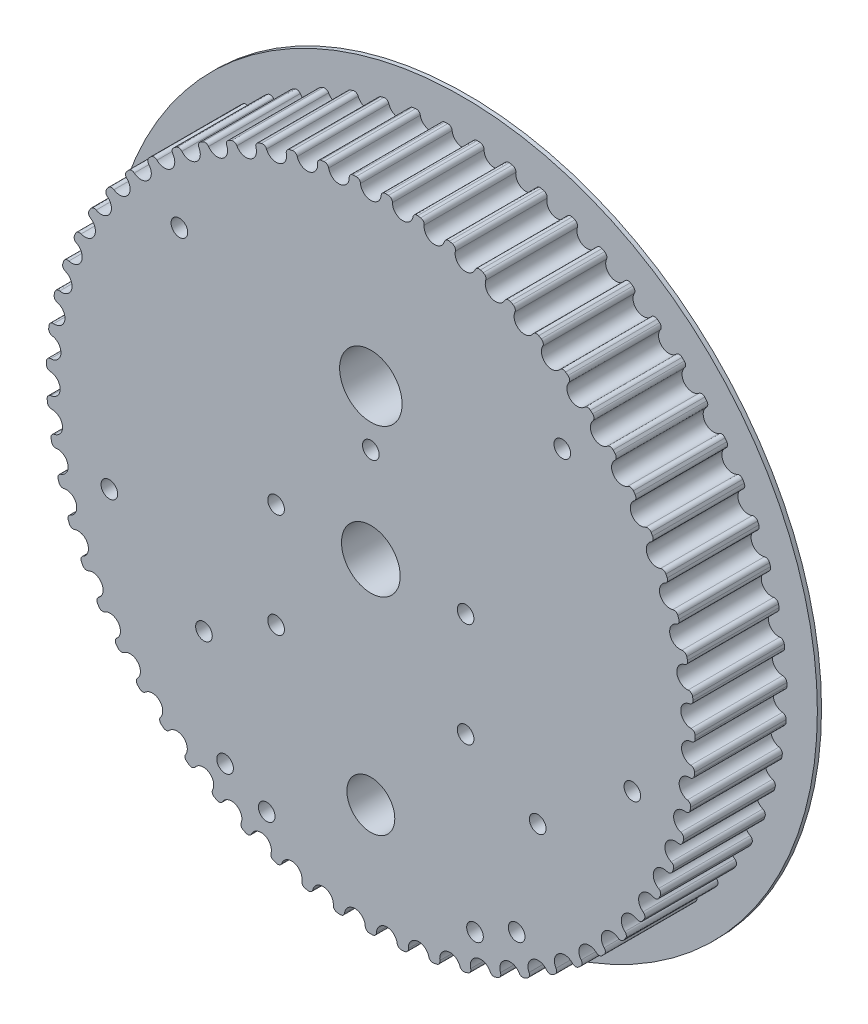
SolidWorks part; units mm, degrees
material "PETG"
ref_plane "Front Plane" through (0, 0, 0) normal (0, 0, 1) x (1, 0, 0)
ref_plane "Top Plane" through (0, 0, 0) normal (0, 1, 0) x (1, 0, 0)
ref_plane "Right Plane" through (0, 0, 0) normal (1, 0, 0) x (0, 0, -1)
sketch "Sketch1" plane through (0, 0, 0) normal (0, 0, 1) x (1, 0, 0)
  line L0 (0, 0) -> (0, 50000) construction
  line L1 (0, 0) -> (3.9983, 80.1144) construction
  line L2 (0, 0) -> (-3.9983, 80.1144) construction
  circle A0 centre (0, 0) radius 80.2141 construction
  arc A1 (-2.4815, 76.9081) -> (2.4815, 76.9081) centre (0, 77.1141) ccw
  arc A2 (3.8832, 77.8073) -> (-3.8832, 77.8073) centre (0, 0) ccw construction
  arc A3 (-2.4815, 76.9081) -> (-3.5233, 77.8244) centre (-3.478, 76.8254) ccw
  arc A4 (3.5233, 77.8244) -> (2.4815, 76.9081) centre (3.478, 76.8254) ccw
  arc A5 (-3.5233, 77.8244) -> (-3.8832, 77.8073) centre (0, 0) ccw
  arc A6 (3.5233, 77.8244) -> (3.8832, 77.8073) centre (0, 0) cw
  arc A7 (4.243, 77.7885) -> (3.8832, 77.8073) centre (0, 0) ccw
  arc A8 (5.1884, 76.773) -> (4.243, 77.7885) centre (4.1886, 76.7899) ccw
  arc A9 (5.1884, 76.773) -> (10.1267, 76.2789) centre (7.6781, 76.7309) ccw
  arc A10 (11.2546, 77.0868) -> (10.1267, 76.2789) centre (11.1101, 76.0973) ccw
  arc A11 (11.2546, 77.0868) -> (11.611, 77.034) centre (0, 0) cw
  arc A12 (11.9672, 76.9794) -> (11.611, 77.034) centre (0, 0) ccw
  arc A13 (12.8068, 75.8749) -> (11.9672, 76.9794) centre (11.8136, 75.9913) ccw
  arc A14 (12.8068, 75.8749) -> (17.6713, 74.8915) centre (15.2799, 75.5851) ccw
  arc A15 (18.874, 75.5832) -> (17.6713, 74.8915) centre (18.6317, 74.613) ccw
  arc A16 (18.874, 75.5832) -> (19.2234, 75.4951) centre (0, 0) cw
  arc A17 (19.5724, 75.4054) -> (19.2234, 75.4951) centre (0, 0) ccw
  arc A18 (20.2978, 74.2227) -> (19.5724, 75.4054) centre (19.3212, 74.4374) ccw
  arc A19 (20.2978, 74.2227) -> (25.0403, 72.7599) centre (22.7298, 73.6881) ccw
  arc A20 (26.3059, 73.3284) -> (25.0403, 72.7599) centre (25.9682, 72.3871) ccw
  arc A21 (26.3059, 73.3284) -> (26.6448, 73.2059) centre (0, 0) cw
  arc A22 (26.9831, 73.0819) -> (26.6448, 73.2059) centre (0, 0) ccw
  arc A23 (27.5872, 71.8329) -> (26.9831, 73.0819) centre (26.6367, 72.1438) ccw
  arc A24 (27.5872, 71.8329) -> (32.1604, 69.9051) centre (29.9538, 71.0588) ccw
  arc A25 (33.4763, 70.3448) -> (32.1604, 69.9051) centre (33.0466, 69.4418) ccw
  arc A26 (33.4763, 70.3448) -> (33.8013, 70.1892) centre (0, 0) cw
  arc A27 (34.1256, 70.0321) -> (33.8013, 70.1892) centre (0, 0) ccw
  arc A28 (34.6023, 68.7291) -> (34.1256, 70.0321) centre (33.6876, 69.1331) ccw
  arc A29 (34.6023, 68.7291) -> (38.9609, 66.3556) centre (36.8801, 67.7233) ccw
  arc A30 (40.314, 66.662) -> (38.9609, 66.3556) centre (39.7965, 65.8063) ccw
  arc A31 (40.314, 66.662) -> (40.6219, 66.4749) centre (0, 0) cw
  arc A32 (40.929, 66.2862) -> (40.6219, 66.4749) centre (0, 0) ccw
  arc A33 (41.2736, 64.9423) -> (40.929, 66.2862) centre (40.4036, 65.4354) ccw
  arc A34 (41.2736, 64.9423) -> (45.3742, 62.1466) centre (43.4399, 63.7147) ccw
  arc A35 (46.7511, 62.3168) -> (45.3742, 62.1466) centre (46.151, 61.5169) ccw
  arc A36 (46.7511, 62.3168) -> (47.0388, 62.0999) centre (0, 0) cw
  arc A37 (47.3256, 61.8816) -> (47.0388, 62.0999) centre (0, 0) ccw
  arc A38 (47.5347, 60.5101) -> (47.3256, 61.8816) centre (46.7181, 61.0873) ccw
  arc A39 (47.5347, 60.5101) -> (51.3365, 57.32) centre (49.568, 59.0728) ccw
  arc A40 (52.7235, 57.3522) -> (51.3365, 57.32) centre (52.0467, 56.616) ccw
  arc A41 (52.7235, 57.3522) -> (52.9882, 57.1077) centre (0, 0) cw
  arc A42 (53.2518, 56.862) -> (52.9882, 57.1077) centre (0, 0) ccw
  arc A43 (53.3233, 55.4765) -> (53.2518, 56.862) centre (52.5683, 56.1321) ccw
  arc A44 (53.3233, 55.4765) -> (56.7886, 51.9237) centre (55.2034, 53.8439) ccw
  arc A45 (58.172, 51.8177) -> (56.7886, 51.9237) centre (57.4253, 51.1525) ccw
  arc A46 (58.172, 51.8177) -> (58.411, 51.548) centre (0, 0) cw
  arc A47 (58.6488, 51.2773) -> (58.411, 51.548) centre (0, 0) ccw
  arc A48 (58.582, 49.8915) -> (58.6488, 51.2773) centre (57.896, 50.6191) ccw
  arc A49 (58.582, 49.8915) -> (61.6764, 46.0113) centre (60.2902, 48.0798) ccw
  arc A50 (63.0423, 45.7681) -> (61.6764, 46.0113) centre (62.233, 45.1806) ccw
  arc A51 (63.0423, 45.7681) -> (63.2533, 45.476) centre (0, 0) cw
  arc A52 (63.463, 45.183) -> (63.2533, 45.476) centre (0, 0) ccw
  arc A53 (63.2585, 43.8107) -> (63.463, 45.183) centre (62.6483, 44.603) ccw
  arc A54 (63.2585, 43.8107) -> (65.9511, 39.6417) centre (64.7778, 41.838) ccw
  arc A55 (67.286, 39.2637) -> (65.9511, 39.6417) centre (66.4223, 38.7597) ccw
  arc A56 (67.286, 39.2637) -> (67.4669, 38.952) centre (0, 0) cw
  arc A57 (67.6464, 38.6396) -> (67.4669, 38.952) centre (0, 0) ccw
  arc A58 (67.3063, 37.2945) -> (67.6464, 38.6396) centre (66.778, 38.1436) ccw
  arc A59 (67.3063, 37.2945) -> (69.5704, 32.8781) centre (68.6217, 35.1803) ccw
  arc A60 (70.8611, 32.3691) -> (69.5704, 32.8781) centre (69.9515, 31.9536) ccw
  arc A61 (70.8611, 32.3691) -> (71.01, 32.0409) centre (0, 0) cw
  arc A62 (71.1575, 31.7122) -> (71.01, 32.0409) centre (0, 0) ccw
  arc A63 (70.6852, 30.4076) -> (71.1575, 31.7122) centre (70.2441, 31.3051) ccw
  arc A64 (70.6852, 30.4076) -> (72.4983, 25.7878) centre (71.7835, 28.1729) ccw
  arc A65 (73.7319, 25.1527) -> (72.4983, 25.7878) centre (72.7854, 24.8299) ccw
  arc A66 (73.7319, 25.1527) -> (73.8474, 24.8114) centre (0, 0) cw
  arc A67 (73.9614, 24.4696) -> (73.8474, 24.8114) centre (0, 0) ccw
  arc A68 (73.3615, 23.2186) -> (73.9614, 24.4696) centre (73.012, 24.1555) ccw
  arc A69 (73.3615, 23.2186) -> (74.7057, 18.4411) centre (74.2319, 20.8856) ccw
  arc A70 (75.8699, 17.6864) -> (74.7057, 18.4411) centre (74.896, 17.4594) ccw
  arc A71 (75.8699, 17.6864) -> (75.9509, 17.3353) centre (0, 0) cw
  arc A72 (76.0302, 16.9838) -> (75.9509, 17.3353) centre (0, 0) ccw
  arc A73 (75.3088, 15.7987) -> (76.0302, 16.9838) centre (75.0543, 16.7658) ccw
  arc A74 (75.3088, 15.7987) -> (76.1706, 10.9112) centre (75.9426, 13.3907) ccw
  arc A75 (77.2539, 10.0443) -> (76.1706, 10.9112) centre (76.2622, 9.9154) ccw
  arc A76 (77.2539, 10.0443) -> (77.2995, 9.6869) centre (0, 0) cw
  arc A77 (77.3435, 9.3292) -> (77.2995, 9.6869) centre (0, 0) ccw
  arc A78 (76.5076, 8.2219) -> (77.3435, 9.3292) centre (76.3507, 9.2095) ccw
  arc A79 (76.5076, 8.2219) -> (76.8785, 3.2728) centre (76.8985, 5.7627) ccw
  arc A80 (77.8701, 2.3024) -> (76.8785, 3.2728) centre (76.8705, 2.2729) ccw
  arc A81 (77.8701, 2.3024) -> (77.8799, 1.9422) centre (0, 0) cw
  arc A82 (77.888, 1.582) -> (77.8799, 1.9422) centre (0, 0) ccw
  arc A83 (76.9461, 0.5633) -> (77.888, 1.582) centre (76.8882, 1.5616) ccw
  arc A84 (76.9461, 0.5633) -> (76.8224, -4.3981) centre (77.0901, -1.9225) ccw
  arc A85 (77.7124, -5.4624) -> (76.8224, -4.3981) centre (76.7148, -5.3923) ccw
  arc A86 (77.7124, -5.4624) -> (77.6863, -5.8218) centre (0, 0) cw
  arc A87 (77.6585, -6.181) -> (77.6863, -5.8218) centre (0, 0) ccw
  arc A88 (76.6198, -7.1008) -> (77.6585, -6.181) centre (76.6616, -6.1017) ccw
  arc A89 (76.6198, -7.1008) -> (76.0027, -12.0252) centre (76.5156, -9.5887) ccw
  arc A90 (76.7823, -13.1729) -> (76.0027, -12.0252) centre (75.7967, -13.0038) ccw
  arc A91 (76.7823, -13.1729) -> (76.7206, -13.5279) centre (0, 0) cw
  arc A92 (76.6572, -13.8826) -> (76.7206, -13.5279) centre (0, 0) ccw
  arc A93 (75.5321, -14.6944) -> (76.6572, -13.8826) centre (75.6732, -13.7044) ccw
  arc A94 (75.5321, -14.6944) -> (74.4277, -19.5329) centre (75.1807, -17.1595) ccw
  arc A95 (75.0892, -20.7525) -> (74.4277, -19.5329) centre (74.1253, -20.4861) ccw
  arc A96 (75.0892, -20.7525) -> (74.9924, -21.0996) centre (0, 0) cw
  arc A97 (74.894, -21.4462) -> (74.9924, -21.0996) centre (0, 0) ccw
  arc A98 (73.6936, -22.142) -> (74.894, -21.4462) centre (73.9326, -21.1709) ccw
  arc A99 (73.6936, -22.142) -> (72.113, -26.8465) centre (73.0986, -24.5598) ccw
  arc A100 (72.6497, -28.1258) -> (72.113, -26.8465) centre (71.7172, -27.7648) ccw
  arc A101 (72.6497, -28.1258) -> (72.5189, -28.4616) centre (0, 0) cw
  arc A102 (72.3865, -28.7967) -> (72.5189, -28.4616) centre (0, 0) ccw
  arc A103 (71.1228, -29.3694) -> (72.3865, -28.7967) centre (71.4573, -28.427) ccw
  arc A104 (71.1228, -29.3694) -> (69.0816, -33.8932) centre (70.2899, -31.716) ccw
  arc A105 (69.4883, -35.2196) -> (69.0816, -33.8932) centre (68.5963, -34.7676) ccw
  arc A106 (69.4883, -35.2196) -> (69.3247, -35.5407) centre (0, 0) cw
  arc A107 (69.1595, -35.861) -> (69.3247, -35.5407) centre (0, 0) ccw
  arc A108 (67.8451, -36.305) -> (69.1595, -35.861) centre (68.2718, -35.4006) ccw
  arc A109 (67.8451, -36.305) -> (65.3637, -40.6031) centre (66.7828, -38.557) ccw
  arc A110 (65.6363, -41.9634) -> (65.3637, -40.6031) centre (64.7937, -41.4248) ccw
  arc A111 (65.6363, -41.9634) -> (65.4415, -42.2666) centre (0, 0) cw
  arc A112 (65.2453, -42.5688) -> (65.4415, -42.2666) centre (0, 0) ccw
  arc A113 (63.8932, -42.8798) -> (65.2453, -42.5688) centre (64.4077, -42.0224) ccw
  arc A114 (63.8932, -42.8798) -> (60.9961, -46.9094) centre (62.6119, -45.0149) ccw
  arc A115 (61.1319, -48.2902) -> (60.9961, -46.9094) centre (60.3472, -47.6703) ccw
  arc A116 (61.1319, -48.2902) -> (60.9079, -48.5724) centre (0, 0) cw
  arc A117 (60.6826, -48.8536) -> (60.9079, -48.5724) centre (0, 0) ccw
  arc A118 (59.3062, -49.0285) -> (60.6826, -48.8536) centre (59.9036, -48.2265) ccw
  arc A119 (59.3062, -49.0285) -> (56.0223, -52.7496) centre (57.8187, -51.0253) ccw
  arc A120 (56.02, -54.137) -> (56.0223, -52.7496) centre (55.3009, -53.442) ccw
  arc A121 (56.02, -54.137) -> (55.769, -54.3955) centre (0, 0) cw
  arc A122 (55.5168, -54.6529) -> (55.769, -54.3955) centre (0, 0) ccw
  arc A123 (54.1299, -54.6898) -> (55.5168, -54.6529) centre (54.8041, -53.9513) ccw
  arc A124 (54.1299, -54.6898) -> (50.4918, -58.0655) centre (52.4509, -56.5286) ccw
  arc A125 (50.3513, -59.4457) -> (50.4918, -58.0655) centre (49.705, -58.6827) ccw
  arc A126 (50.3513, -59.4457) -> (50.0758, -59.678) centre (0, 0) cw
  arc A127 (49.7992, -59.909) -> (50.0758, -59.678) centre (0, 0) ccw
  arc A128 (48.4155, -59.8076) -> (49.7992, -59.909) centre (49.16, -59.14) ccw
  arc A129 (48.4155, -59.8076) -> (44.4594, -62.8043) centre (46.5618, -61.4701) ccw
  arc A130 (44.1822, -64.1637) -> (44.4594, -62.8043) centre (43.6151, -63.3401) ccw
  arc A131 (44.1822, -64.1637) -> (43.8849, -64.3674) centre (0, 0) cw
  arc A132 (43.5867, -64.5697) -> (43.8849, -64.3674) centre (0, 0) ccw
  arc A133 (42.22, -64.3311) -> (43.5867, -64.5697) centre (43.0272, -63.7408) ccw
  arc A134 (42.22, -64.3311) -> (37.9852, -66.9189) centre (40.21, -65.8008) ccw
  arc A135 (37.574, -68.244) -> (37.9852, -66.9189) centre (37.0917, -67.368) ccw
  arc A136 (37.574, -68.244) -> (37.2579, -68.4171) centre (0, 0) cw
  arc A137 (36.9411, -68.5887) -> (37.2579, -68.4171) centre (0, 0) ccw
  arc A138 (35.6049, -68.2152) -> (36.9411, -68.5887) centre (36.4669, -67.7082) ccw
  arc A139 (35.6049, -68.2152) -> (31.1335, -70.3685) centre (33.4586, -69.4774) ccw
  arc A140 (30.5924, -71.646) -> (31.1335, -70.3685) centre (30.1997, -70.7264) ccw
  arc A141 (30.5924, -71.646) -> (30.2607, -71.7868) centre (0, 0) cw
  arc A142 (29.9283, -71.926) -> (30.2607, -71.7868) centre (0, 0) ccw
  arc A143 (28.6359, -71.4213) -> (29.9283, -71.926) centre (29.5441, -71.0027) ccw
  arc A144 (28.6359, -71.4213) -> (23.9723, -73.1187) centre (26.3746, -72.4635) ccw
  arc A145 (23.3067, -74.336) -> (23.9723, -73.1187) centre (23.0075, -73.3818) ccw
  arc A146 (23.3067, -74.336) -> (22.9626, -74.443) centre (0, 0) cw
  arc A147 (22.6181, -74.5484) -> (22.9626, -74.443) centre (0, 0) ccw
  arc A148 (21.3824, -73.9176) -> (22.6181, -74.5484) centre (22.3277, -73.5915) ccw
  arc A149 (21.3824, -73.9176) -> (16.5729, -75.1422) centre (19.0285, -74.7295) ccw
  arc A150 (15.7894, -76.2872) -> (16.5729, -75.1422) centre (15.5867, -75.308) ccw
  arc A151 (15.7894, -76.2872) -> (15.4364, -76.3594) centre (0, 0) cw
  arc A152 (15.083, -76.43) -> (15.4364, -76.3594) centre (0, 0) ccw
  arc A153 (13.9163, -75.6793) -> (15.083, -76.43) centre (14.8894, -75.449) ccw
  arc A154 (13.9163, -75.6793) -> (9.0088, -76.419) centre (11.4933, -76.2528) ccw
  arc A155 (8.1152, -77.4803) -> (9.0088, -76.419) centre (8.011, -76.4857) ccw
  arc A156 (8.1152, -77.4803) -> (7.7567, -77.517) centre (0, 0) cw
  arc A157 (7.3981, -77.552) -> (7.7567, -77.517) centre (0, 0) ccw
  arc A158 (6.3119, -76.6888) -> (7.3981, -77.552) centre (7.3031, -76.5565) ccw
  arc A159 (6.3119, -76.6888) -> (1.3552, -76.9362) centre (3.8438, -77.0182) ccw
  arc A160 (0.3603, -77.9033) -> (1.3552, -76.9362) centre (0.3557, -76.9033) ccw
  arc A161 (0.3603, -77.9033) -> (0, -77.9041) centre (0, 0) cw
  arc A162 (-0.3603, -77.9033) -> (0, -77.9041) centre (0, 0) ccw
  arc A163 (-1.3552, -76.9362) -> (-0.3603, -77.9033) centre (-0.3557, -76.9033) ccw
  arc A164 (-1.3552, -76.9362) -> (-6.3119, -76.6888) centre (-3.8438, -77.0182) ccw
  arc A165 (-7.3981, -77.552) -> (-6.3119, -76.6888) centre (-7.3031, -76.5565) ccw
  arc A166 (-7.3981, -77.552) -> (-7.7567, -77.517) centre (0, 0) cw
  arc A167 (-8.1152, -77.4803) -> (-7.7567, -77.517) centre (0, 0) ccw
  arc A168 (-9.0088, -76.419) -> (-8.1152, -77.4803) centre (-8.011, -76.4857) ccw
  arc A169 (-9.0088, -76.419) -> (-13.9163, -75.6793) centre (-11.4933, -76.2528) ccw
  arc A170 (-15.083, -76.43) -> (-13.9163, -75.6793) centre (-14.8894, -75.449) ccw
  arc A171 (-15.083, -76.43) -> (-15.4364, -76.3594) centre (0, 0) cw
  arc A172 (-15.7894, -76.2872) -> (-15.4364, -76.3594) centre (0, 0) ccw
  arc A173 (-16.5729, -75.1422) -> (-15.7894, -76.2872) centre (-15.5867, -75.308) ccw
  arc A174 (-16.5729, -75.1422) -> (-21.3824, -73.9176) centre (-19.0285, -74.7295) ccw
  arc A175 (-22.6181, -74.5484) -> (-21.3824, -73.9176) centre (-22.3277, -73.5915) ccw
  arc A176 (-22.6181, -74.5484) -> (-22.9626, -74.443) centre (0, 0) cw
  arc A177 (-23.3067, -74.336) -> (-22.9626, -74.443) centre (0, 0) ccw
  arc A178 (-23.9723, -73.1187) -> (-23.3067, -74.336) centre (-23.0075, -73.3818) ccw
  arc A179 (-23.9723, -73.1187) -> (-28.6359, -71.4213) centre (-26.3746, -72.4635) ccw
  arc A180 (-29.9283, -71.926) -> (-28.6359, -71.4213) centre (-29.5441, -71.0027) ccw
  arc A181 (-29.9283, -71.926) -> (-30.2607, -71.7868) centre (0, 0) cw
  arc A182 (-30.5924, -71.646) -> (-30.2607, -71.7868) centre (0, 0) ccw
  arc A183 (-31.1335, -70.3685) -> (-30.5924, -71.646) centre (-30.1997, -70.7264) ccw
  arc A184 (-31.1335, -70.3685) -> (-35.6049, -68.2152) centre (-33.4586, -69.4774) ccw
  arc A185 (-36.9411, -68.5887) -> (-35.6049, -68.2152) centre (-36.4669, -67.7082) ccw
  arc A186 (-36.9411, -68.5887) -> (-37.2579, -68.4171) centre (0, 0) cw
  arc A187 (-37.574, -68.244) -> (-37.2579, -68.4171) centre (0, 0) ccw
  arc A188 (-37.9852, -66.9189) -> (-37.574, -68.244) centre (-37.0917, -67.368) ccw
  arc A189 (-37.9852, -66.9189) -> (-42.22, -64.3311) centre (-40.21, -65.8008) ccw
  arc A190 (-43.5867, -64.5697) -> (-42.22, -64.3311) centre (-43.0272, -63.7408) ccw
  arc A191 (-43.5867, -64.5697) -> (-43.8849, -64.3674) centre (0, 0) cw
  arc A192 (-44.1822, -64.1637) -> (-43.8849, -64.3674) centre (0, 0) ccw
  arc A193 (-44.4594, -62.8043) -> (-44.1822, -64.1637) centre (-43.6151, -63.3401) ccw
  arc A194 (-44.4594, -62.8043) -> (-48.4155, -59.8076) centre (-46.5618, -61.4701) ccw
  arc A195 (-49.7992, -59.909) -> (-48.4155, -59.8076) centre (-49.16, -59.14) ccw
  arc A196 (-49.7992, -59.909) -> (-50.0758, -59.678) centre (0, 0) cw
  arc A197 (-50.3513, -59.4457) -> (-50.0758, -59.678) centre (0, 0) ccw
  arc A198 (-50.4918, -58.0655) -> (-50.3513, -59.4457) centre (-49.705, -58.6827) ccw
  arc A199 (-50.4918, -58.0655) -> (-54.1299, -54.6898) centre (-52.4509, -56.5286) ccw
  arc A200 (-55.5168, -54.6529) -> (-54.1299, -54.6898) centre (-54.8041, -53.9513) ccw
  arc A201 (-55.5168, -54.6529) -> (-55.769, -54.3955) centre (0, 0) cw
  arc A202 (-56.02, -54.137) -> (-55.769, -54.3955) centre (0, 0) ccw
  arc A203 (-56.0223, -52.7496) -> (-56.02, -54.137) centre (-55.3009, -53.442) ccw
  arc A204 (-56.0223, -52.7496) -> (-59.3062, -49.0285) centre (-57.8187, -51.0253) ccw
  arc A205 (-60.6826, -48.8536) -> (-59.3062, -49.0285) centre (-59.9036, -48.2265) ccw
  arc A206 (-60.6826, -48.8536) -> (-60.9079, -48.5724) centre (0, 0) cw
  arc A207 (-61.1319, -48.2902) -> (-60.9079, -48.5724) centre (0, 0) ccw
  arc A208 (-60.9961, -46.9094) -> (-61.1319, -48.2902) centre (-60.3472, -47.6703) ccw
  arc A209 (-60.9961, -46.9094) -> (-63.8932, -42.8798) centre (-62.6119, -45.0149) ccw
  arc A210 (-65.2453, -42.5688) -> (-63.8932, -42.8798) centre (-64.4077, -42.0224) ccw
  arc A211 (-65.2453, -42.5688) -> (-65.4415, -42.2666) centre (0, 0) cw
  arc A212 (-65.6363, -41.9634) -> (-65.4415, -42.2666) centre (0, 0) ccw
  arc A213 (-65.3637, -40.6031) -> (-65.6363, -41.9634) centre (-64.7937, -41.4248) ccw
  arc A214 (-65.3637, -40.6031) -> (-67.8451, -36.305) centre (-66.7828, -38.557) ccw
  arc A215 (-69.1595, -35.861) -> (-67.8451, -36.305) centre (-68.2718, -35.4006) ccw
  arc A216 (-69.1595, -35.861) -> (-69.3247, -35.5407) centre (0, 0) cw
  arc A217 (-69.4883, -35.2196) -> (-69.3247, -35.5407) centre (0, 0) ccw
  arc A218 (-69.0816, -33.8932) -> (-69.4883, -35.2196) centre (-68.5963, -34.7676) ccw
  arc A219 (-69.0816, -33.8932) -> (-71.1228, -29.3694) centre (-70.2899, -31.716) ccw
  arc A220 (-72.3865, -28.7967) -> (-71.1228, -29.3694) centre (-71.4573, -28.427) ccw
  arc A221 (-72.3865, -28.7967) -> (-72.5189, -28.4616) centre (0, 0) cw
  arc A222 (-72.6497, -28.1258) -> (-72.5189, -28.4616) centre (0, 0) ccw
  arc A223 (-72.113, -26.8465) -> (-72.6497, -28.1258) centre (-71.7172, -27.7648) ccw
  arc A224 (-72.113, -26.8465) -> (-73.6936, -22.142) centre (-73.0986, -24.5598) ccw
  arc A225 (-74.894, -21.4462) -> (-73.6936, -22.142) centre (-73.9326, -21.1709) ccw
  arc A226 (-74.894, -21.4462) -> (-74.9924, -21.0996) centre (0, 0) cw
  arc A227 (-75.0892, -20.7525) -> (-74.9924, -21.0996) centre (0, 0) ccw
  arc A228 (-74.4277, -19.5329) -> (-75.0892, -20.7525) centre (-74.1253, -20.4861) ccw
  arc A229 (-74.4277, -19.5329) -> (-75.5321, -14.6944) centre (-75.1807, -17.1595) ccw
  arc A230 (-76.6572, -13.8826) -> (-75.5321, -14.6944) centre (-75.6732, -13.7044) ccw
  arc A231 (-76.6572, -13.8826) -> (-76.7206, -13.5279) centre (0, 0) cw
  arc A232 (-76.7823, -13.1729) -> (-76.7206, -13.5279) centre (0, 0) ccw
  arc A233 (-76.0027, -12.0252) -> (-76.7823, -13.1729) centre (-75.7967, -13.0038) ccw
  arc A234 (-76.0027, -12.0252) -> (-76.6198, -7.1008) centre (-76.5156, -9.5887) ccw
  arc A235 (-77.6585, -6.181) -> (-76.6198, -7.1008) centre (-76.6616, -6.1017) ccw
  arc A236 (-77.6585, -6.181) -> (-77.6863, -5.8218) centre (0, 0) cw
  arc A237 (-77.7124, -5.4624) -> (-77.6863, -5.8218) centre (0, 0) ccw
  arc A238 (-76.8224, -4.3981) -> (-77.7124, -5.4624) centre (-76.7148, -5.3923) ccw
  arc A239 (-76.8224, -4.3981) -> (-76.9461, 0.5633) centre (-77.0901, -1.9225) ccw
  arc A240 (-77.888, 1.582) -> (-76.9461, 0.5633) centre (-76.8882, 1.5616) ccw
  arc A241 (-77.888, 1.582) -> (-77.8799, 1.9422) centre (0, 0) cw
  arc A242 (-77.8701, 2.3024) -> (-77.8799, 1.9422) centre (0, 0) ccw
  arc A243 (-76.8785, 3.2728) -> (-77.8701, 2.3024) centre (-76.8705, 2.2729) ccw
  arc A244 (-76.8785, 3.2728) -> (-76.5076, 8.2219) centre (-76.8985, 5.7627) ccw
  arc A245 (-77.3435, 9.3292) -> (-76.5076, 8.2219) centre (-76.3507, 9.2095) ccw
  arc A246 (-77.3435, 9.3292) -> (-77.2995, 9.6869) centre (0, 0) cw
  arc A247 (-77.2539, 10.0443) -> (-77.2995, 9.6869) centre (0, 0) ccw
  arc A248 (-76.1706, 10.9112) -> (-77.2539, 10.0443) centre (-76.2622, 9.9154) ccw
  arc A249 (-76.1706, 10.9112) -> (-75.3088, 15.7987) centre (-75.9426, 13.3907) ccw
  arc A250 (-76.0302, 16.9838) -> (-75.3088, 15.7987) centre (-75.0543, 16.7658) ccw
  arc A251 (-76.0302, 16.9838) -> (-75.9509, 17.3353) centre (0, 0) cw
  arc A252 (-75.8699, 17.6864) -> (-75.9509, 17.3353) centre (0, 0) ccw
  arc A253 (-74.7057, 18.4411) -> (-75.8699, 17.6864) centre (-74.896, 17.4594) ccw
  arc A254 (-74.7057, 18.4411) -> (-73.3615, 23.2186) centre (-74.2319, 20.8856) ccw
  arc A255 (-73.9614, 24.4696) -> (-73.3615, 23.2186) centre (-73.012, 24.1555) ccw
  arc A256 (-73.9614, 24.4696) -> (-73.8474, 24.8114) centre (0, 0) cw
  arc A257 (-73.7319, 25.1527) -> (-73.8474, 24.8114) centre (0, 0) ccw
  arc A258 (-72.4983, 25.7878) -> (-73.7319, 25.1527) centre (-72.7854, 24.8299) ccw
  arc A259 (-72.4983, 25.7878) -> (-70.6852, 30.4076) centre (-71.7835, 28.1729) ccw
  arc A260 (-71.1575, 31.7122) -> (-70.6852, 30.4076) centre (-70.2441, 31.3051) ccw
  arc A261 (-71.1575, 31.7122) -> (-71.01, 32.0409) centre (0, 0) cw
  arc A262 (-70.8611, 32.3691) -> (-71.01, 32.0409) centre (0, 0) ccw
  arc A263 (-69.5704, 32.8781) -> (-70.8611, 32.3691) centre (-69.9515, 31.9536) ccw
  arc A264 (-69.5704, 32.8781) -> (-67.3063, 37.2945) centre (-68.6217, 35.1803) ccw
  arc A265 (-67.6464, 38.6396) -> (-67.3063, 37.2945) centre (-66.778, 38.1436) ccw
  arc A266 (-67.6464, 38.6396) -> (-67.4669, 38.952) centre (0, 0) cw
  arc A267 (-67.286, 39.2637) -> (-67.4669, 38.952) centre (0, 0) ccw
  arc A268 (-65.9511, 39.6417) -> (-67.286, 39.2637) centre (-66.4223, 38.7597) ccw
  arc A269 (-65.9511, 39.6417) -> (-63.2585, 43.8107) centre (-64.7778, 41.838) ccw
  arc A270 (-63.463, 45.183) -> (-63.2585, 43.8107) centre (-62.6483, 44.603) ccw
  arc A271 (-63.463, 45.183) -> (-63.2533, 45.476) centre (0, 0) cw
  arc A272 (-63.0423, 45.7681) -> (-63.2533, 45.476) centre (0, 0) ccw
  arc A273 (-61.6764, 46.0113) -> (-63.0423, 45.7681) centre (-62.233, 45.1806) ccw
  arc A274 (-61.6764, 46.0113) -> (-58.582, 49.8915) centre (-60.2902, 48.0798) ccw
  arc A275 (-58.6488, 51.2773) -> (-58.582, 49.8915) centre (-57.896, 50.6191) ccw
  arc A276 (-58.6488, 51.2773) -> (-58.411, 51.548) centre (0, 0) cw
  arc A277 (-58.172, 51.8177) -> (-58.411, 51.548) centre (0, 0) ccw
  arc A278 (-56.7886, 51.9237) -> (-58.172, 51.8177) centre (-57.4253, 51.1525) ccw
  arc A279 (-56.7886, 51.9237) -> (-53.3233, 55.4765) centre (-55.2034, 53.8439) ccw
  arc A280 (-53.2518, 56.862) -> (-53.3233, 55.4765) centre (-52.5683, 56.1321) ccw
  arc A281 (-53.2518, 56.862) -> (-52.9882, 57.1077) centre (0, 0) cw
  arc A282 (-52.7235, 57.3522) -> (-52.9882, 57.1077) centre (0, 0) ccw
  arc A283 (-51.3365, 57.32) -> (-52.7235, 57.3522) centre (-52.0467, 56.616) ccw
  arc A284 (-51.3365, 57.32) -> (-47.5347, 60.5101) centre (-49.568, 59.0728) ccw
  arc A285 (-47.3256, 61.8816) -> (-47.5347, 60.5101) centre (-46.7181, 61.0873) ccw
  arc A286 (-47.3256, 61.8816) -> (-47.0388, 62.0999) centre (0, 0) cw
  arc A287 (-46.7511, 62.3168) -> (-47.0388, 62.0999) centre (0, 0) ccw
  arc A288 (-45.3742, 62.1466) -> (-46.7511, 62.3168) centre (-46.151, 61.5169) ccw
  arc A289 (-45.3742, 62.1466) -> (-41.2736, 64.9423) centre (-43.4399, 63.7147) ccw
  arc A290 (-40.929, 66.2862) -> (-41.2736, 64.9423) centre (-40.4036, 65.4354) ccw
  arc A291 (-40.929, 66.2862) -> (-40.6219, 66.4749) centre (0, 0) cw
  arc A292 (-40.314, 66.662) -> (-40.6219, 66.4749) centre (0, 0) ccw
  arc A293 (-38.9609, 66.3556) -> (-40.314, 66.662) centre (-39.7965, 65.8063) ccw
  arc A294 (-38.9609, 66.3556) -> (-34.6023, 68.7291) centre (-36.8801, 67.7233) ccw
  arc A295 (-34.1256, 70.0321) -> (-34.6023, 68.7291) centre (-33.6876, 69.1331) ccw
  arc A296 (-34.1256, 70.0321) -> (-33.8013, 70.1892) centre (0, 0) cw
  arc A297 (-33.4763, 70.3448) -> (-33.8013, 70.1892) centre (0, 0) ccw
  arc A298 (-32.1604, 69.9051) -> (-33.4763, 70.3448) centre (-33.0466, 69.4418) ccw
  arc A299 (-32.1604, 69.9051) -> (-27.5872, 71.8329) centre (-29.9538, 71.0588) ccw
  arc A300 (-26.9831, 73.0819) -> (-27.5872, 71.8329) centre (-26.6367, 72.1438) ccw
  arc A301 (-26.9831, 73.0819) -> (-26.6448, 73.2059) centre (0, 0) cw
  arc A302 (-26.3059, 73.3284) -> (-26.6448, 73.2059) centre (0, 0) ccw
  arc A303 (-25.0403, 72.7599) -> (-26.3059, 73.3284) centre (-25.9682, 72.3871) ccw
  arc A304 (-25.0403, 72.7599) -> (-20.2978, 74.2227) centre (-22.7298, 73.6881) ccw
  arc A305 (-19.5724, 75.4054) -> (-20.2978, 74.2227) centre (-19.3212, 74.4374) ccw
  arc A306 (-19.5724, 75.4054) -> (-19.2234, 75.4951) centre (0, 0) cw
  arc A307 (-18.874, 75.5832) -> (-19.2234, 75.4951) centre (0, 0) ccw
  arc A308 (-17.6713, 74.8915) -> (-18.874, 75.5832) centre (-18.6317, 74.613) ccw
  arc A309 (-17.6713, 74.8915) -> (-12.8068, 75.8749) centre (-15.2799, 75.5851) ccw
  arc A310 (-11.9672, 76.9794) -> (-12.8068, 75.8749) centre (-11.8136, 75.9913) ccw
  arc A311 (-11.9672, 76.9794) -> (-11.611, 77.034) centre (0, 0) cw
  arc A312 (-11.2546, 77.0868) -> (-11.611, 77.034) centre (0, 0) ccw
  arc A313 (-10.1267, 76.2789) -> (-11.2546, 77.0868) centre (-11.1101, 76.0973) ccw
  arc A314 (-10.1267, 76.2789) -> (-5.1884, 76.773) centre (-7.6781, 76.7309) ccw
  arc A315 (-4.243, 77.7885) -> (-5.1884, 76.773) centre (-4.1886, 76.7899) ccw
  arc A316 (-4.243, 77.7885) -> (-3.8832, 77.8073) centre (0, 0) cw
  point P9 (0, 74.6241)
  point P11 (0, 80.2141)
  point P12 (0, 77.9041)
  dimension "D1" = 160.4282
  dimension "D6" = 1
  dimension "D3" = 2.49
  dimension "D4" = 5.59
  dimension "D5" = 3.28
  dimension "D2" = 8
  dimension "D7" = 63
extrude "Boss-Extrude1" add sketch "Sketch1" along normal blind 22 contours A316 A315 A314 A313 A312 A311 A310 A309 A308 A307 A306 A305 A304 A303 A302 A301 A300 A299 A298 A297 A296 A295 A294 A293 A292 A291 A290 A289 A288 A287 A286 A285 A284 A283 A282 A281 A280 A279 A278 A277 A276 A275 A274 A273 A272 A271 A270 A269 A268 A267 A266 region at (0, 0, 0)
sketch "Sketch2" plane through (0, 0, 0) normal (0, 0, -1) x (-1, 0, 0)
  circle A0 centre (0, 0) radius 85.2141
  dimension "D1" = 170.4282
extrude "Boss-Extrude2" add sketch "Sketch2" along normal blind 1
sketch "Sketch3" plane through (0, 0, 22) normal (0, 0, 1) x (1, 0, 0)
  circle A0 centre (0, 0) radius 7.05
  circle A1 centre (0, -51.05) radius 5.75
  circle A2 centre (0, 36) radius 7.5
  dimension "D1" = 14.1
  dimension "D2" = 15
  dimension "D4" = 11.5
  dimension "D3" = 36
  dimension "D5" = 51.05
extrude "Cut-Extrude1" cut sketch "Sketch3" against normal through all
sketch "Sketch4" plane through (0, 0, 22) normal (0, 0, 1) x (1, 0, 0)
  line L0 (0, 0) -> (0, 50000) construction
  line L1 (0, 0) -> (-45.9619, 45.9619) construction
  line L2 (0, 0) -> (45.9619, 45.9619) construction
  line L3 (0, 0) -> (-62.7852, -16.8232) construction
  line L4 (0, 0) -> (62.7852, -16.8232) construction
  line L5 (-22.75, -25) -> (-40.0705, -35) construction
  line L6 (22.75, -25) -> (40.0705, -35) construction
  circle A0 centre (-45.9619, 45.9619) radius 2
  circle A1 centre (45.9619, 45.9619) radius 2
  circle A2 centre (-25, -65) radius 2
  circle A3 centre (25, -65) radius 2
  circle A4 centre (-62.7852, -16.8232) radius 2
  circle A5 centre (62.7852, -16.8232) radius 2
  circle A6 centre (-35, -60) radius 2
  circle A7 centre (35, -60) radius 2
  circle A8 centre (-22.75, 0) radius 2
  circle A9 centre (22.75, 0) radius 2
  circle A10 centre (0, 22.75) radius 2
  circle A11 centre (-22.75, -25) radius 2
  circle A12 centre (22.75, -25) radius 2
  circle A13 centre (-40.0705, -35) radius 2
  circle A14 centre (40.0705, -35) radius 2
  dimension "D1" = 4
  dimension "D2" = 65
  dimension "D3" = 45
  dimension "D4" = 25
  dimension "D5" = 65
  dimension "D6" = 25
  dimension "D7" = 60
  dimension "D8" = 35
  dimension "D9" = 60
  dimension "D10" = 35
  dimension "D11" = 22.75
  dimension "D12" = 22.75
  dimension "D13" = 22.75
  dimension "D14" = 25
  dimension "D15" = 60
  dimension "D16" = 20
extrude "Cut-Extrude2" cut sketch "Sketch4" against normal blind 18
equation "\"tol_dia_id_intfc\"= 0.0500mm ' For hole diameters - Interference fit"
equation "\"tol_dia_id_slip\"= 0.0750mm ' For hole diameters - Slip fit"
equation "\"tol_dia_id_clear\"= 0.1000mm ' For hole diameters - Clearance fit"
equation "\"tol_dia_od_intfc\"= 0.0500mm ' For shaft diameters - Interference fit"
equation "\"tol_dia_od_slip\"= 0.0750mm ' For shaft diameters - Slip fit"
equation "\"tol_dia_od_clear\"= 0.1000mm ' For shaft diameters - Clearance fit"
equation "\"tol_general_intfc\"= 0.0250mm ' For general parts (Horiz) - Interference fit"
equation "\"tol_general_slip\"= 0.0375mm ' For general parts (Horiz) - Slip fit"
equation "\"tol_general_clear\"= 0.0500mm ' For general parts (Horiz) - Clearance fit"
equation "\"tol_layer_intfc\"= 0.0250mm ' For all parts (Vert) - Interference fit"
equation "\"tol_layer_slip\"= 0.0375mm ' For all parts (Vert) - Slip fit"
equation "\"tol_layer_clear\"= 0.0500mm ' For all parts (Vert) - Clearance fit"
equation "\"tol_corner_rad\"= 0.100mm ' For corners that fit into other parts"
equation "\"pitch\"= 8mm"
equation "\"n\"= 63"
equation "\"pitch_dia\"= \"pitch\" * \"n\" / PI"
equation "\"belt_width\"= 22mm"
equation "\"D1@Sketch1\"=\"pitch_dia\""
equation "\"D2@Sketch1\"=\"pitch\""
equation "\"D7@Sketch1\"=\"n\""
equation "\"D1@Extrude-Thin2\"=\"belt_width\""
equation "\"D1@Boss-Extrude1\"=\"belt_width\""
equation "\"D1@Sketch2\"=\"pitch_dia\"+10"
equation "\"D1@Sketch3\"=14.00mm + \"tol_dia_id_clear\""
equation "\"D1@Sketch4\"=3.95+\"tol_dia_id_intfc\""
equation "\"D6@Sketch4\"=\"D4@Sketch4\""
equation "\"D10@Sketch4\"=\"D8@Sketch4\""
equation "\"D12@Sketch4\"=\"D11@Sketch4\""
equation "\"D13@Sketch4\"=\"D11@Sketch4\""
